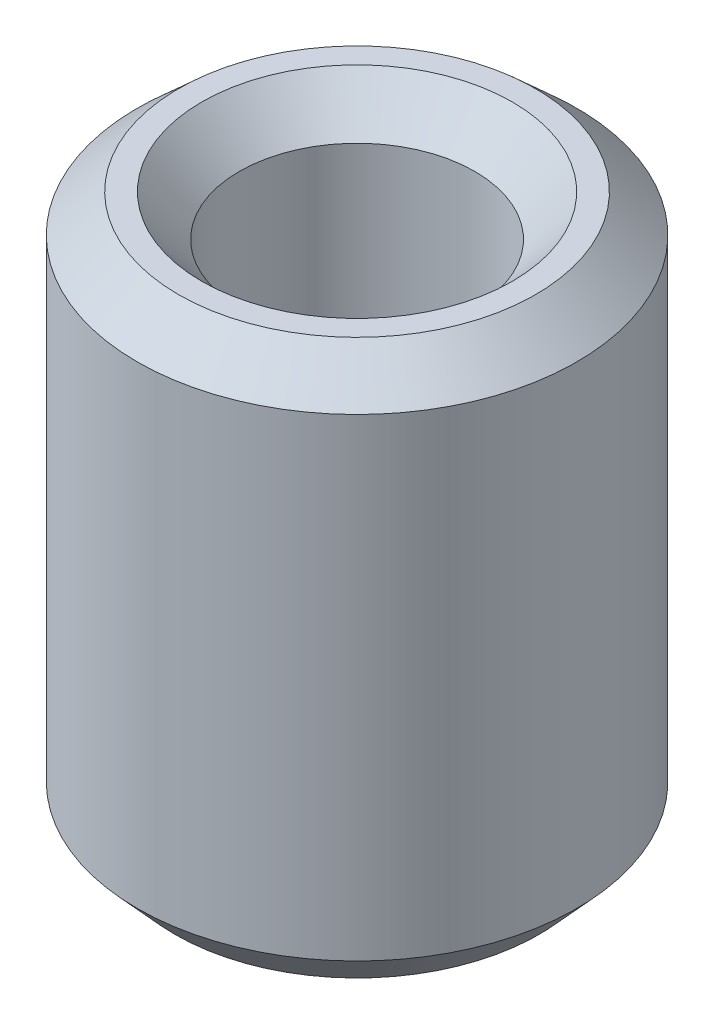
SolidWorks part; units mm, degrees
ref_plane "Front Plane" through (0, 0, 0) normal (0, 0, 1) x (1, 0, 0)
ref_plane "Top Plane" through (0, 0, 0) normal (0, 1, 0) x (1, 0, 0)
ref_plane "Right Plane" through (0, 0, 0) normal (1, 0, 0) x (0, 0, -1)
sketch "Sketch1" plane through (0, 0, 0) normal (0, 1, 0) x (1, 0, 0)
  circle A0 centre (0, 0) radius 15
  dimension "SLEEVE_OD" = 30
extrude "Boss-Extrude1" add sketch "Sketch1" along normal blind 37.6919
sketch "Sketch2" plane through (0, 0, 0) normal (0, 1, 0) x (1, 0, 0)
  circle A0 centre (0, 0) radius 8.0344
  dimension "BORE_D" = 16.0689
extrude "Cut-Extrude1" cut sketch "Sketch2" along normal through all
chamfer "Chamfer1" distance 2.5669 angle 47.681 4 edges at (0, 37.6919, 8.0344) (0, 0, 8.0344) (0, 0, 15) (0, 37.6919, 15) first distance on face at (0, 37.6919, 8.0344) first distance on face at (0, 0, 8.0344) first distance on face at (0, 37.6919, 15)
